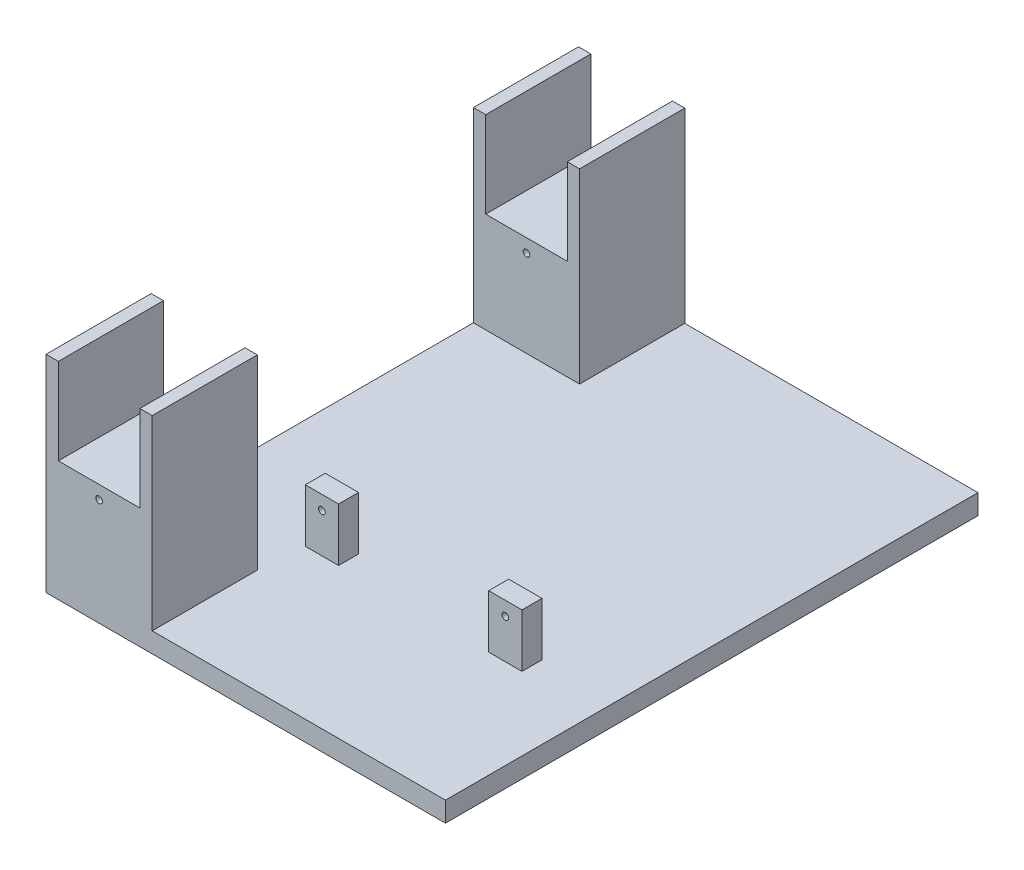
SolidWorks part; units mm, degrees
ref_plane "Front Plane" through (0, 0, 0) normal (0, 0, 1) x (1, 0, 0)
ref_plane "Top Plane" through (0, 0, 0) normal (0, 1, 0) x (1, 0, 0)
ref_plane "Right Plane" through (0, 0, 0) normal (1, 0, 0) x (0, 0, -1)
sketch "Sketch1" plane through (0, 0, 0) normal (0, 1, 0) x (1, 0, 0)
  line L1 (-30, 40) -> (30, 40)
  line L2 (-30, 40) -> (-30, -40)
  line L3 (-30, -40) -> (30, -40)
  line L4 (30, 40) -> (30, -40)
  point P4 (0, 40)
  point P6 (-30, 0)
  dimension "D1" = 80
  dimension "D2" = 60
extrude "Boss-Extrude1" add sketch "Sketch1" along normal blind 3
sketch "Sketch3" plane through (0, 0, 0) normal (0, 0, 1) x (1, 0, 0)
  line L3 (-30, 3) -> (30, 3) construction
  line L47 (-30, 3) -> (-28.15, 3)
  line L52 (-30, 3) -> (-30, 31)
  line L53 (-30, 31) -> (-28.15, 31)
  line L54 (-28.15, 3) -> (-28.15, 31)
  line L55 (-28.15, 3) -> (-15.9, 3)
  line L56 (-28.15, 3) -> (-28.15, 18.0562)
  line L57 (-28.15, 18.0562) -> (-15.9, 18.0562)
  line L58 (-15.9, 3) -> (-15.9, 18.0562)
  line L59 (-15.9, 3) -> (-14.05, 3)
  line L60 (-15.9, 3) -> (-15.9, 31)
  line L61 (-15.9, 31) -> (-14.05, 31)
  line L62 (-14.05, 3) -> (-14.05, 31)
  circle A32 centre (-22.025, 16.0562) radius 0.5
  point P2 (-22.025, 18.0562)
  dimension "D5" = 1
  dimension "D2" = 12.25
  dimension "D3" = 15.0562
  dimension "D4" = 13.0562
  dimension "D6" = 28
  dimension "D7" = 1.85
  dimension "D8" = 28
  dimension "D1" = 1.85
extrude "Boss-Extrude2" add sketch "Sketch3" against normal blind 15.8 from surface contours L59 L62 L61 L60 L58 | A32 L57 L54 L55 L58 | A32 L57 | L47 L54 L53 L52 region at (-29.075, 17, 0) region at (-22.025, 10.5044, 0) region at (-14.975, 17, 0) starting at face at (0, 1.5, 40)
extrude "Boss-Extrude3" add sketch "Sketch3<3>" along normal blind 15.8 from surface contours L59 L62 L61 L60 L58 | A32 L57 L54 L55 L58 | L47 L54 L53 L52 | A32 L57 region at (-29.075, 17, 0) region at (-22.025, 10.5044, 0) region at (-14.975, 17, 0) starting at face at (0, 1.5, -40)
sketch "Sketch3<3>" plane through (0, 0, 0) normal (0, 0, 1) x (1, 0, 0) same geometry as "Sketch3"
sketch "Sketch4" plane through (0, 0, 0) normal (0, 0, 1) x (1, 0, 0)
  line L50 (30, 3) -> (-14.05, 3) construction
  line L51 (19, 11) -> (14, 11)
  line L52 (19, 11) -> (19, 3)
  line L53 (19, 3) -> (14, 3)
  line L54 (14, 11) -> (14, 3)
  line L55 (-14.05, 3) -> (-14.05, 31) construction
  line L56 (-13.55, 11) -> (-8.55, 11)
  line L57 (-13.55, 11) -> (-13.55, 3)
  line L58 (-13.55, 3) -> (-8.55, 3)
  line L59 (-8.55, 11) -> (-8.55, 3)
  circle A30 centre (16.5, 8.9) radius 0.5
  circle A31 centre (-11.05, 8.9) radius 0.5
  point P0 (-11.05, 11)
  point P3 (16.5, 11)
  dimension "D5" = 1
  dimension "D6" = 1
  dimension "D1" = 22.55
  dimension "D2" = 2.1
  dimension "D3" = 5
  dimension "D4" = 5
  dimension "D7" = 8
  dimension "D8" = 8
  dimension "D9" = 2.1
  dimension "D10" = 0.5
extrude "Boss-Extrude4" add sketch "Sketch4" along normal blind 3 from offset 14.5 contours A30 L54 L53 L52 L51 | A30 L51 L54 | A31 L59 L56 | A31 L56 L57 L58 L59 region at (16.5, 6.9619, 0) region at (-11.05, 6.9619, 0)
